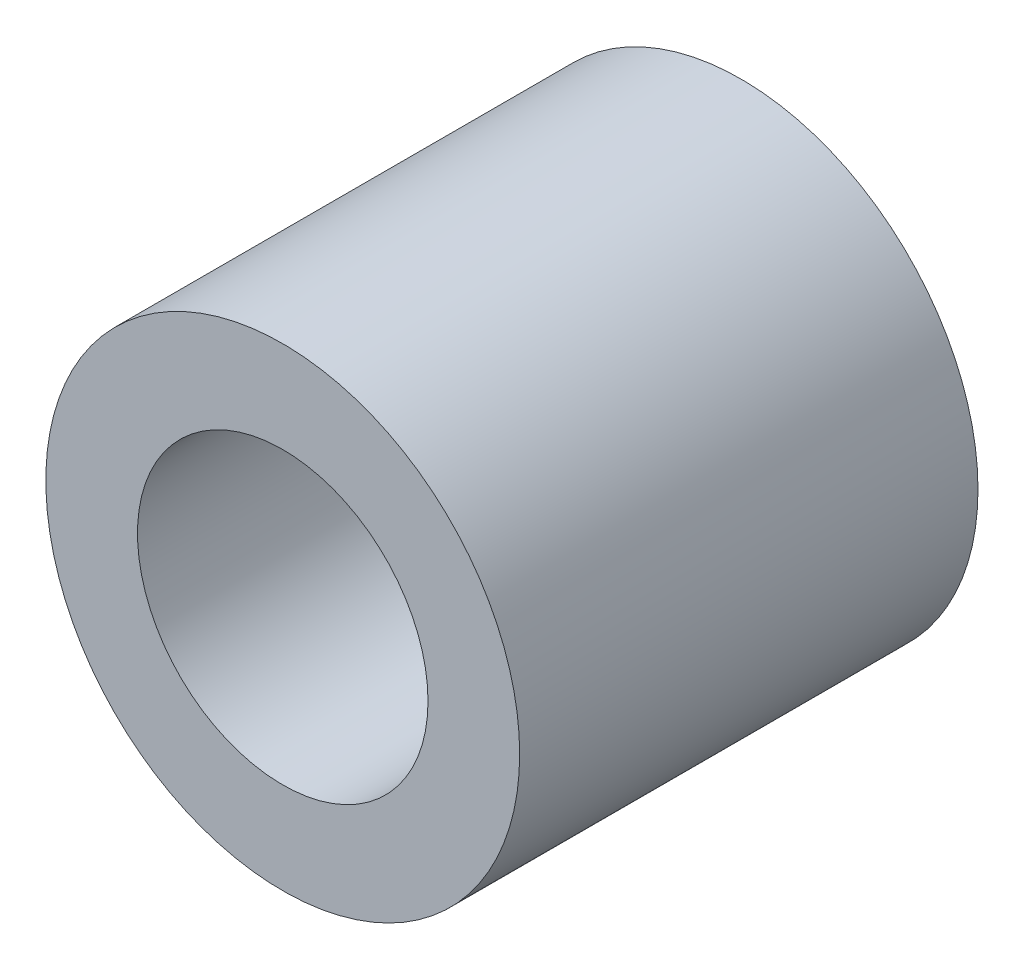
SolidWorks part; units mm, degrees
ref_plane "Front Plane" through (0, 0, 0) normal (0, 0, 1) x (1, 0, 0)
ref_plane "Top Plane" through (0, 0, 0) normal (0, 1, 0) x (1, 0, 0)
ref_plane "Right Plane" through (0, 0, 0) normal (1, 0, 0) x (0, 0, -1)
sketch "Sketch1" plane through (0, 0, 0) normal (0, 0, 1) x (1, 0, 0)
  circle A0 centre (0, 0) radius 4.025
  circle A1 centre (0, 0) radius 6.565
  dimension "D1" = 8.05
  dimension "D2" = 2.54
extrude "Boss-Extrude1" add sketch "Sketch1" along normal blind 12.7
